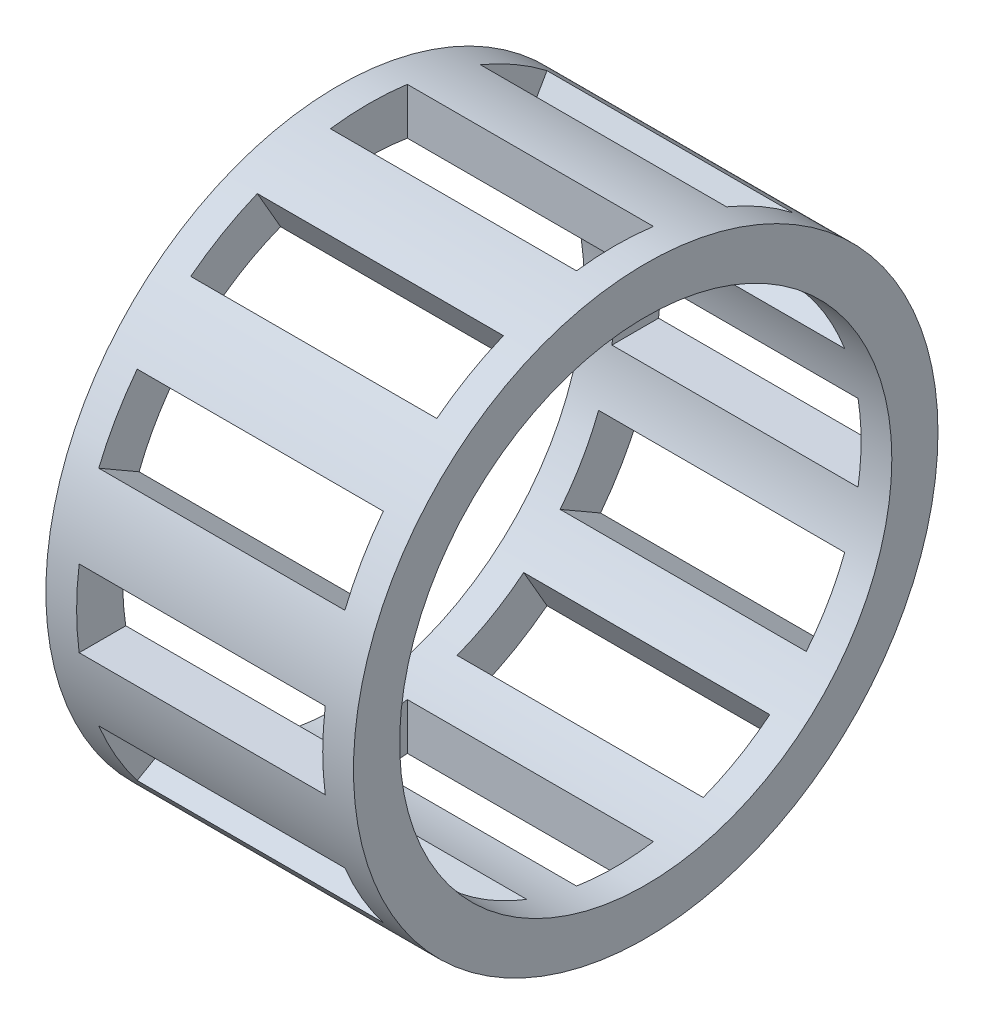
SolidWorks part; units mm, degrees
note: '?' marks a value the reader was unsure of.
ref_plane "Face" through (0, 0, 0) normal (0, 0, 1) x (1, 0, 0)
ref_plane "Dessus" through (0, 0, 0) normal (0, 1, 0) x (1, 0, 0)
ref_plane "Droite" through (0, 0, 0) normal (1, 0, 0) x (0, 0, -1)
sketch "Esquisse1" plane through (0, 0, 0) normal (0, 0, 1) x (1, 0, 0)
  line L0 (11.7, 0) -> (-8.7, 0) construction
  line L2 (-5, 9.5) -> (5, 9.5)
  line L3 (-5, 9.5) -> (-5, 8)
  line L4 (-5, 8) -> (5, 8)
  line L5 (5, 9.5) -> (5, 8)
  point P7 (0, 8)
  dimension "D1" = 16
  dimension "D2" = 19
  dimension "D3" = 10
revolve "Base-Révolution" add sketch "Esquisse1" angle 360 about L0
sketch "Esquisse2" plane through (0, 0, 0) normal (0, 0, 1) x (1, 0, 0)
  line L0 (0, -9.8) -> (0, 11.3) construction
  line L1 (-4, 1.25) -> (4, 1.25)
  line L2 (-4, 1.25) -> (-4, -1.25)
  line L3 (-4, -1.25) -> (4, -1.25)
  line L4 (4, 1.25) -> (4, -1.25)
  line L5 (6.5, 0) -> (-6.7, 0) construction
  line L6 (11.7, 0) -> (-8.7, 0) construction
  dimension "D2" = 8
  dimension "D3" = 2.5
extrude "Enlèv. mat.-Extru.1" cut sketch "Esquisse2" against normal through all
ref_axis "Axe1" through (-50, 0, 0) along (1, 0, 0)?
pattern_circular "Répétition circulaire1" count 12 over 360 about axis through (-50, 0, 0) along (1, 0, 0)
